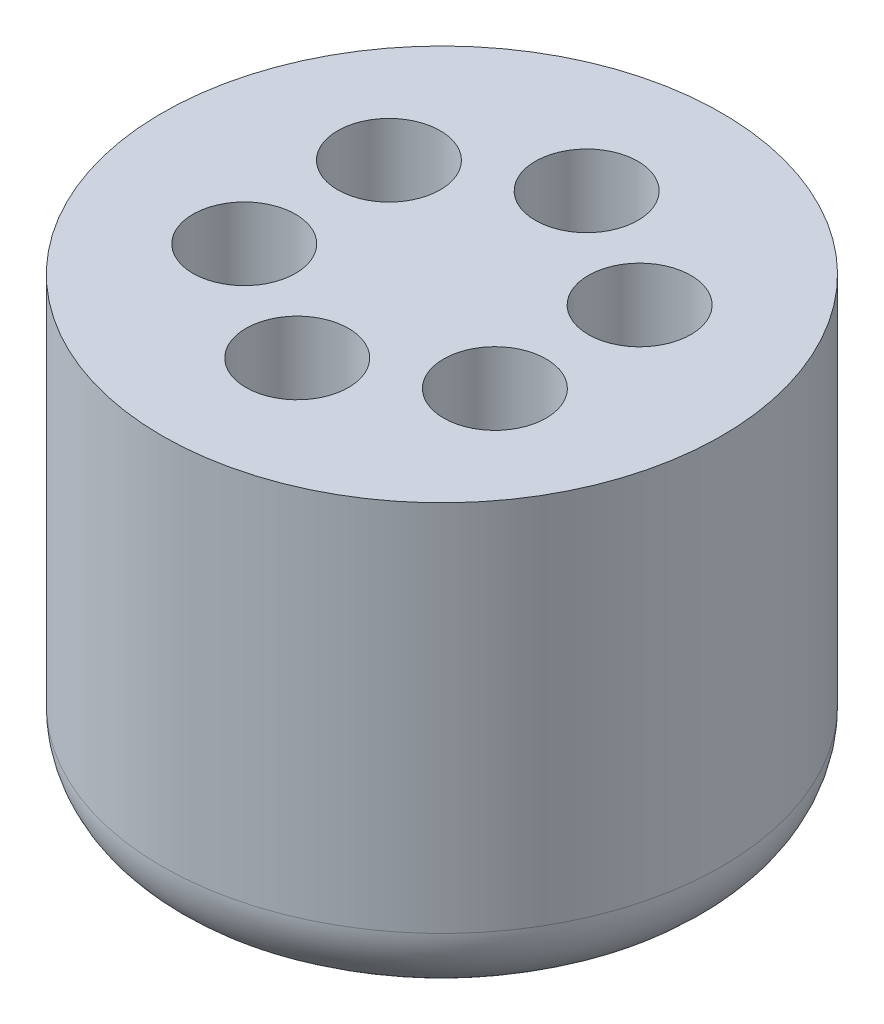
SolidWorks part; units mm, degrees
ref_plane "Front Plane" through (0, 0, 0) normal (0, 0, 1) x (1, 0, 0)
ref_plane "Top Plane" through (0, 0, 0) normal (0, 1, 0) x (1, 0, 0)
ref_plane "Right Plane" through (0, 0, 0) normal (1, 0, 0) x (0, 0, -1)
sketch "Sketch1" plane through (0, 0, 0) normal (0, 1, 0) x (1, 0, 0)
  circle A0 centre (0, 0) radius 30
extrude "Boss-Extrude1" add sketch "Sketch1" along normal blind 48
sketch "Sketch2" plane through (0, 48, 0) normal (0, 1, 0) x (1, 0, 0)
  circle A0 centre (0, 15.52) radius 5.5
  circle A2 centre (-13.4407, 7.76) radius 5.5
  circle A3 centre (-13.4407, -7.76) radius 5.5
  circle A4 centre (0, -15.52) radius 5.5
  circle A5 centre (13.4407, -7.76) radius 5.5
  circle A6 centre (13.4407, 7.76) radius 5.5
  dimension "D1" = 15.52
extrude "Cut-Extrude1" cut sketch "Sketch2" against normal blind 32
fillet "Fillet1" radius 8 1 edges at (0, 0, 30)
extrude "Cut-Extrude2" cut sketch "Sketch2<3>" against normal blind 35
sketch "Sketch2<3>" plane through (0, 48, 0) normal (0, 1, 0) x (1, 0, 0) same geometry as "Sketch2"
